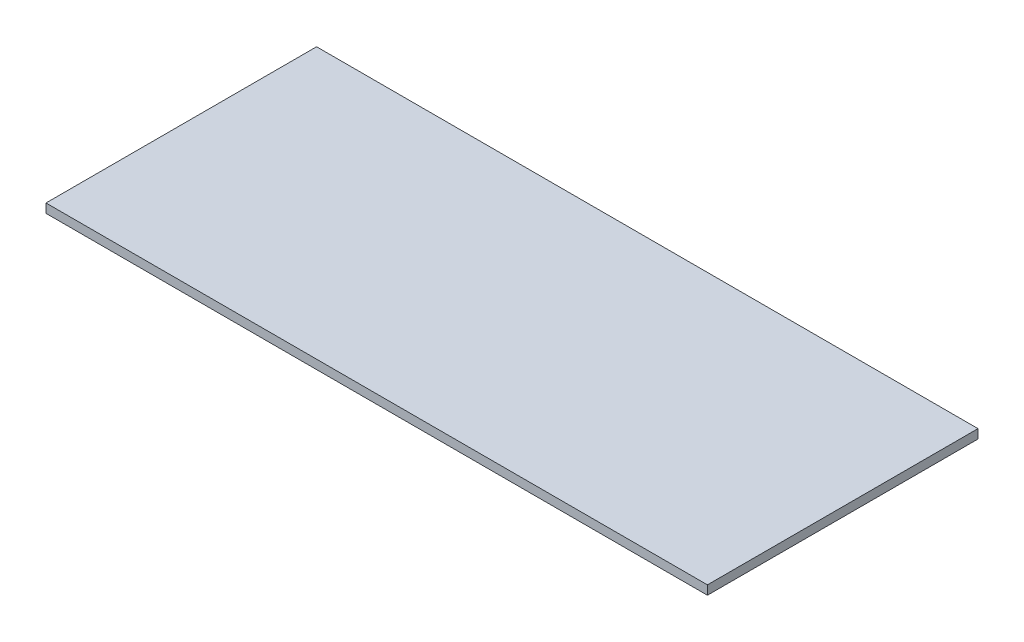
SolidWorks part; units mm, degrees
ref_plane "Front Plane" through (0, 0, 0) normal (0, 0, 1) x (1, 0, 0)
ref_plane "Top Plane" through (0, 0, 0) normal (0, 1, 0) x (1, 0, 0)
ref_plane "Right Plane" through (0, 0, 0) normal (1, 0, 0) x (0, 0, -1)
sketch "Sketch2" plane through (0, 0, 0) normal (0, 1, 0) x (1, 0, 0)
  line L3 (110, 45) -> (-110, 45)
  line L4 (110, 45) -> (110, -45)
  line L5 (110, -45) -> (-110, -45)
  line L6 (-110, 45) -> (-110, -45)
  line L7 (110, 45) -> (-110, -45) construction
  line L8 (110, -45) -> (-110, 45) construction
  point P0 (0, 0)
  dimension "D1" = 220
  dimension "D2" = 90
extrude "Boss-Extrude1" add sketch "Sketch2" along normal blind 3
